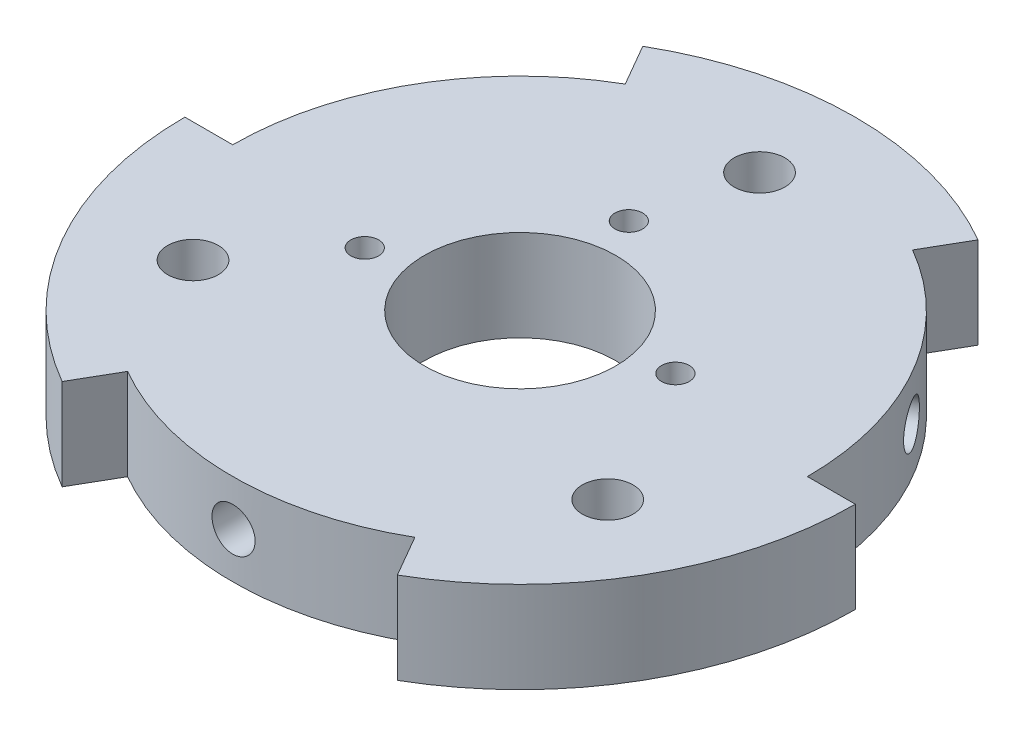
SolidWorks part; units mm, degrees
ref_plane "Front Plane" through (0, 0, 0) normal (0, 0, 1) x (1, 0, 0)
ref_plane "Top Plane" through (0, 0, 0) normal (0, 1, 0) x (1, 0, 0)
ref_plane "Right Plane" through (0, 0, 0) normal (1, 0, 0) x (0, 0, -1)
sketch "Baseplate Sketch" plane through (0, 0, 0) normal (0, 1, 0) x (1, 0, 0)
  line L0 (0, 0) -> (0, 61.4504) construction
  line L1 (-17.5, 30.3109) -> (-15, 25.9808)
  line L2 (17.5, 30.3109) -> (15, 25.9808)
  line L3 (-17.5, 30.3109) -> (-21.8301, 27.8109) construction
  line L4 (17.5, 30.3109) -> (13.1699, 32.8109) construction
  line L5 (17.5, -30.3109) -> (15, -25.9808)
  line L6 (35, 0) -> (30, 0)
  line L7 (-35, 0) -> (-30, 0)
  line L8 (-17.5, -30.3109) -> (-15, -25.9808)
  circle A0 centre (0, 0) radius 30
  circle A1 centre (0, 0) radius 10
  arc A2 (-17.5, 30.3109) -> (17.5, 30.3109) centre (0, 0) cw
  arc A3 (35, 0) -> (17.5, -30.3109) centre (0, 0) cw
  arc A4 (-17.5, -30.3109) -> (-35, 0) centre (0, 0) cw
  circle A5 centre (0, 25) radius 2.65
  circle A6 centre (21.6506, -12.5) radius 2.65
  circle A7 centre (-21.6506, -12.5) radius 2.65
  point P15 (0, 35)
  point P25 (0, 0)
  point P31 (0, 0)
  dimension "D1" = 60
  dimension "D2" = 20
  dimension "D3" = 35
  dimension "D4" = 90
  dimension "D5" = 5
  dimension "D12" = 5.3
  dimension "D6" = 5
  dimension "D7" = 90
  dimension "D8" = 60
  dimension "D9" = 5
  dimension "D10" = 5
  dimension "D14" = 25
  dimension "D11" = 3
  dimension "D13" = 3
extrude "Boss-Extrude1" add sketch "Baseplate Sketch" along normal blind 9.525 contours A4 L8 A0 L7 | A3 L6 A0 L5 | A2 L1 A0 L2 | A0 | A1 | A6 | A7 | A5 region at (0, 0, -31.0964) region at (-26.9303, 0, 15.5482) region at (26.9303, 0, 15.5482)
ref_plane "Plane1" through (0, 0, 40) normal (0, 0, 1) x (1, 0, 0)
sketch "Sketch2" plane through (0, 0, 40) normal (0, 0, 1) x (1, 0, 0)
  line L0 (0, 9.525) -> (0, 0) construction
  line L4 (15, 9.525) -> (-15, 9.525)
  line L5 (-15, 9.525) -> (-15, 0)
  line L6 (-15, 0) -> (15, 0)
  line L7 (15, 0) -> (15, 9.525)
  line L8 (15, 9.525) -> (-15, 9.525) construction
  line L9 (-15, 9.525) -> (-15, 0) construction
  line L10 (-15, 0) -> (15, 0) construction
  line L11 (15, 0) -> (15, 9.525) construction
  circle A0 centre (0, 4.7625) radius 2.25
  dimension "D1" = 0
  dimension "D2" = 4.5
extrude "Cut-Extrude1" cut sketch "Sketch2" against normal blind 25
pattern_circular "CirPattern1" count 3 over 360 about axis through (0, 9.525, 0) along (0, 1, 0) of "Cut-Extrude1"
sketch "Sketch3" plane through (0, 9.525, 0) normal (0, 1, 0) x (1, 0, 0)
  line L0 (0, 0) -> (39.0113, 0) construction
  line L1 (9.8481, 1.7365) -> (13.7873, 2.4311)
  line L2 (0, 0) -> (-1.247, -0.2199) construction
  circle A0 centre (2.4311, -13.7873) radius 1.45 construction
  circle A1 centre (13.7873, 2.4311) radius 1.45
  circle A2 centre (0, 0) radius 10 construction
  circle A3 centre (-13.7873, -2.4311) radius 1.45
  circle A4 centre (-2.4311, 13.7873) radius 1.45
  point P20 (0, 0)
  dimension "D1" = 2.9
  dimension "D2" = 4
  dimension "D3" = 10
  dimension "D4" = 4
extrude "Cut-Extrude2" cut sketch "Sketch3" against normal up to surface (9.525 mm away) contours A4 | A1 | A3 region at (13.9101, 9.525, -1.0274) region at (-13.7873, 9.525, 2.4311) region at (-2.4311, 9.525, -13.7873) up to face at (0, 0, 0)
